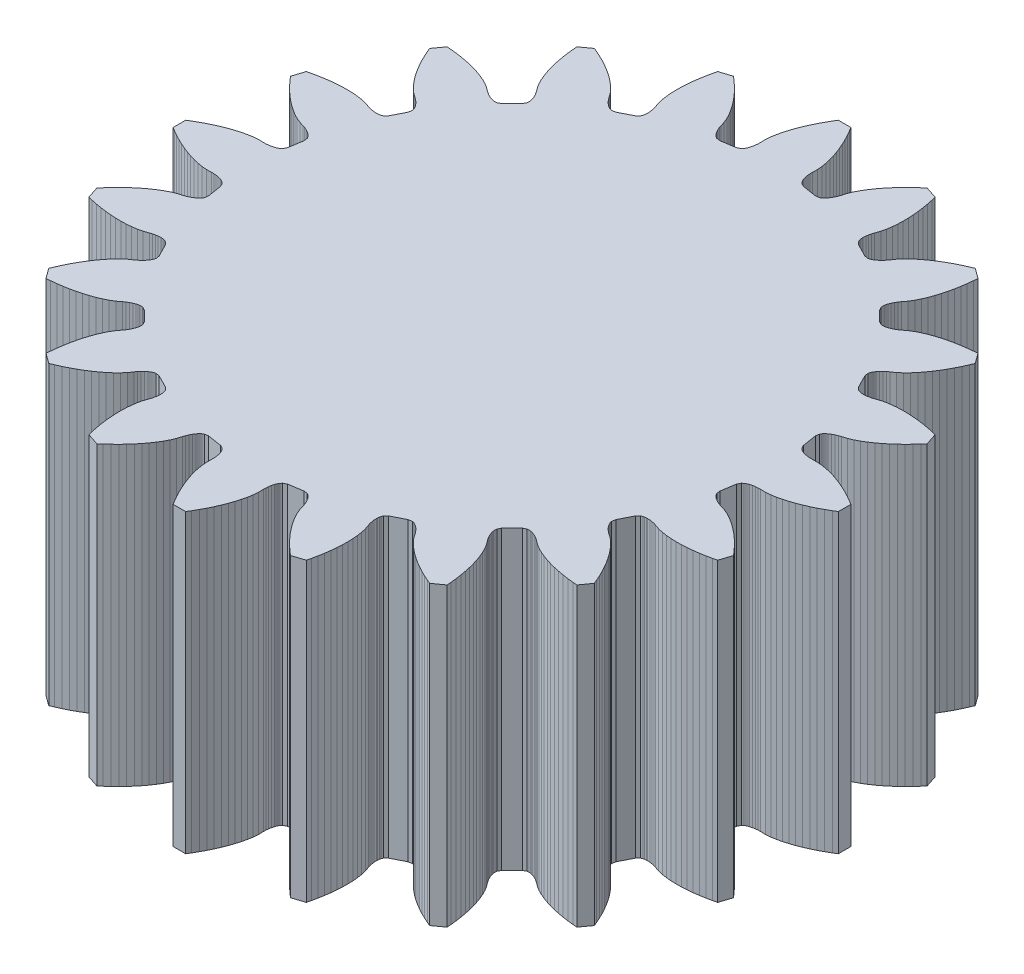
SolidWorks part; units mm, degrees
ref_plane "Front Plane" through (0, 0, 0) normal (0, 0, 1) x (1, 0, 0)
ref_plane "Top Plane" through (0, 0, 0) normal (0, 1, 0) x (1, 0, 0)
ref_plane "Right Plane" through (0, 0, 0) normal (1, 0, 0) x (0, 0, -1)
sketch "Sketch1" plane through (0, 0, 0) normal (0, 1, 0) x (1, 0, 0)
  line L0 (19.9269, 12.3554) -> (19.9815, 12.2461)
  line L1 (19.9815, 12.2461) -> (20.0271, 12.2067)
  line L2 (20.0271, 12.2067) -> (20.0711, 12.1796)
  line L3 (20.0711, 12.1796) -> (20.1144, 12.1591)
  line L4 (20.1144, 12.1591) -> (20.1571, 12.1432)
  line L5 (20.1571, 12.1432) -> (20.2414, 12.1206)
  line L6 (20.2414, 12.1206) -> (20.3248, 12.107)
  line L7 (20.3248, 12.107) -> (20.4075, 12.1)
  line L8 (20.4075, 12.1) -> (20.4897, 12.0984)
  line L9 (20.4897, 12.0984) -> (20.6534, 12.1025)
  line L10 (20.6534, 12.1025) -> (20.8187, 12.0882)
  line L11 (20.8187, 12.0882) -> (20.9851, 12.06)
  line L12 (20.9851, 12.06) -> (21.1522, 12.0208)
  line L13 (21.1522, 12.0208) -> (21.3198, 11.9721)
  line L14 (21.3198, 11.9721) -> (21.4876, 11.9147)
  line L15 (21.4876, 11.9147) -> (21.6554, 11.8491)
  line L16 (21.6554, 11.8491) -> (21.823, 11.7758)
  line L17 (21.823, 11.7758) -> (21.9904, 11.695)
  line L18 (21.9904, 11.695) -> (22.1573, 11.6069)
  line L19 (22.1573, 11.6069) -> (22.3236, 11.5119)
  line L20 (22.3236, 11.5119) -> (22.4478, 11.4361)
  line L21 (22.4478, 11.4361) -> (22.4478, 11.0138)
  line L22 (22.4478, 11.0138) -> (22.3236, 10.9379)
  line L23 (22.3236, 10.9379) -> (22.1573, 10.8429)
  line L24 (22.1573, 10.8429) -> (21.9904, 10.7549)
  line L25 (21.9904, 10.7549) -> (21.823, 10.6741)
  line L26 (21.823, 10.6741) -> (21.6554, 10.6007)
  line L27 (21.6554, 10.6007) -> (21.4876, 10.5351)
  line L28 (21.4876, 10.5351) -> (21.3198, 10.4777)
  line L29 (21.3198, 10.4777) -> (21.1522, 10.429)
  line L30 (21.1522, 10.429) -> (20.9851, 10.3898)
  line L31 (20.9851, 10.3898) -> (20.8187, 10.3616)
  line L32 (20.8187, 10.3616) -> (20.6534, 10.3473)
  line L33 (20.6534, 10.3473) -> (20.4897, 10.3514)
  line L34 (20.4897, 10.3514) -> (20.4075, 10.3498)
  line L35 (20.4075, 10.3498) -> (20.3248, 10.3428)
  line L36 (20.3248, 10.3428) -> (20.2414, 10.3292)
  line L37 (20.2414, 10.3292) -> (20.1571, 10.3066)
  line L38 (20.1571, 10.3066) -> (20.1144, 10.2907)
  line L39 (20.1144, 10.2907) -> (20.0711, 10.2703)
  line L40 (20.0711, 10.2703) -> (20.0271, 10.2431)
  line L41 (20.0271, 10.2431) -> (19.9815, 10.2037)
  line L42 (19.9815, 10.2037) -> (19.9269, 10.0944)
  line L43 (19.9269, 10.0944) -> (19.8503, 9.611)
  line L44 (19.8503, 9.611) -> (19.8685, 9.4902)
  line L45 (19.8685, 9.4902) -> (19.8997, 9.4386)
  line L46 (19.8997, 9.4386) -> (19.9332, 9.3992)
  line L47 (19.9332, 9.3992) -> (19.968, 9.3664)
  line L48 (19.968, 9.3664) -> (20.0037, 9.338)
  line L49 (20.0037, 9.338) -> (20.0769, 9.2905)
  line L50 (20.0769, 9.2905) -> (20.152, 9.2518)
  line L51 (20.152, 9.2518) -> (20.2285, 9.2196)
  line L52 (20.2285, 9.2196) -> (20.3062, 9.1927)
  line L53 (20.3062, 9.1927) -> (20.4631, 9.146)
  line L54 (20.4631, 9.146) -> (20.6159, 9.0813)
  line L55 (20.6159, 9.0813) -> (20.7655, 9.003)
  line L56 (20.7655, 9.003) -> (20.9123, 8.9141)
  line L57 (20.9123, 8.9141) -> (21.0566, 8.8161)
  line L58 (21.0566, 8.8161) -> (21.1984, 8.7096)
  line L59 (21.1984, 8.7096) -> (21.3378, 8.5954)
  line L60 (21.3378, 8.5954) -> (21.4746, 8.4738)
  line L61 (21.4746, 8.4738) -> (21.6088, 8.3452)
  line L62 (21.6088, 8.3452) -> (21.7403, 8.2099)
  line L63 (21.7403, 8.2099) -> (21.8691, 8.0681)
  line L64 (21.8691, 8.0681) -> (21.9638, 7.9577)
  line L65 (21.9638, 7.9577) -> (21.8333, 7.556)
  line L66 (21.8333, 7.556) -> (21.6917, 7.5223)
  line L67 (21.6917, 7.5223) -> (21.5042, 7.4833)
  line L68 (21.5042, 7.4833) -> (21.3183, 7.4511)
  line L69 (21.3183, 7.4511) -> (21.1341, 7.426)
  line L70 (21.1341, 7.426) -> (20.952, 7.4081)
  line L71 (20.952, 7.4081) -> (20.7721, 7.3975)
  line L72 (20.7721, 7.3975) -> (20.5948, 7.3948)
  line L73 (20.5948, 7.3948) -> (20.4204, 7.4002)
  line L74 (20.4204, 7.4002) -> (20.2493, 7.4146)
  line L75 (20.2493, 7.4146) -> (20.0824, 7.4392)
  line L76 (20.0824, 7.4392) -> (19.9207, 7.4767)
  line L77 (19.9207, 7.4767) -> (19.7663, 7.5312)
  line L78 (19.7663, 7.5312) -> (19.6877, 7.555)
  line L79 (19.6877, 7.555) -> (19.6068, 7.5739)
  line L80 (19.6068, 7.5739) -> (19.5233, 7.5868)
  line L81 (19.5233, 7.5868) -> (19.4362, 7.5914)
  line L82 (19.4362, 7.5914) -> (19.3906, 7.5894)
  line L83 (19.3906, 7.5894) -> (19.3432, 7.5834)
  line L84 (19.3432, 7.5834) -> (19.2929, 7.5712)
  line L85 (19.2929, 7.5712) -> (19.2373, 7.5477)
  line L86 (19.2373, 7.5477) -> (19.1516, 7.4607)
  line L87 (19.1516, 7.4607) -> (18.9294, 7.0246)
  line L88 (18.9294, 7.0246) -> (18.9094, 6.9041)
  line L89 (18.9094, 6.9041) -> (18.9231, 6.8454)
  line L90 (18.9231, 6.8454) -> (18.9428, 6.7976)
  line L91 (18.9428, 6.7976) -> (18.9657, 6.7556)
  line L92 (18.9657, 6.7556) -> (18.9909, 6.7176)
  line L93 (18.9909, 6.7176) -> (19.0459, 6.6498)
  line L94 (19.0459, 6.6498) -> (19.1054, 6.5898)
  line L95 (19.1054, 6.5898) -> (19.1682, 6.5355)
  line L96 (19.1682, 6.5355) -> (19.2337, 6.4859)
  line L97 (19.2337, 6.4859) -> (19.3685, 6.393)
  line L98 (19.3685, 6.393) -> (19.4938, 6.2843)
  line L99 (19.4938, 6.2843) -> (19.6119, 6.1636)
  line L100 (19.6119, 6.1636) -> (19.7241, 6.0337)
  line L101 (19.7241, 6.0337) -> (19.831, 5.8958)
  line L102 (19.831, 5.8958) -> (19.933, 5.7507)
  line L103 (19.933, 5.7507) -> (20.0302, 5.599)
  line L104 (20.0302, 5.599) -> (20.1228, 5.4411)
  line L105 (20.1228, 5.4411) -> (20.2107, 5.2774)
  line L106 (20.2107, 5.2774) -> (20.294, 5.1081)
  line L107 (20.294, 5.1081) -> (20.3726, 4.9334)
  line L108 (20.3726, 4.9334) -> (20.4286, 4.7991)
  line L109 (20.4286, 4.7991) -> (20.1803, 4.4574)
  line L110 (20.1803, 4.4574) -> (20.0353, 4.4691)
  line L111 (20.0353, 4.4691) -> (19.8449, 4.4899)
  line L112 (19.8449, 4.4899) -> (19.6581, 4.5168)
  line L113 (19.6581, 4.5168) -> (19.4752, 4.5498)
  line L114 (19.4752, 4.5498) -> (19.2964, 4.589)
  line L115 (19.2964, 4.589) -> (19.1221, 4.6346)
  line L116 (19.1221, 4.6346) -> (18.9526, 4.6868)
  line L117 (18.9526, 4.6868) -> (18.7885, 4.7459)
  line L118 (18.7885, 4.7459) -> (18.6302, 4.8124)
  line L119 (18.6302, 4.8124) -> (18.479, 4.8874)
  line L120 (18.479, 4.8874) -> (18.3369, 4.973)
  line L121 (18.3369, 4.973) -> (18.2069, 5.0725)
  line L122 (18.2069, 5.0725) -> (18.1394, 5.1195)
  line L123 (18.1394, 5.1195) -> (18.0684, 5.1625)
  line L124 (18.0684, 5.1625) -> (17.9929, 5.2005)
  line L125 (17.9929, 5.2005) -> (17.9114, 5.2318)
  line L126 (17.9114, 5.2318) -> (17.8675, 5.244)
  line L127 (17.8675, 5.244) -> (17.8205, 5.2529)
  line L128 (17.8205, 5.2529) -> (17.7689, 5.2568)
  line L129 (17.7689, 5.2568) -> (17.7089, 5.2517)
  line L130 (17.7089, 5.2517) -> (17.6005, 5.1954)
  line L131 (17.6005, 5.1954) -> (17.2544, 4.8494)
  line L132 (17.2544, 4.8494) -> (17.1981, 4.7409)
  line L133 (17.1981, 4.7409) -> (17.193, 4.6809)
  line L134 (17.193, 4.6809) -> (17.1969, 4.6293)
  line L135 (17.1969, 4.6293) -> (17.2058, 4.5823)
  line L136 (17.2058, 4.5823) -> (17.218, 4.5384)
  line L137 (17.218, 4.5384) -> (17.2493, 4.4569)
  line L138 (17.2493, 4.4569) -> (17.2873, 4.3814)
  line L139 (17.2873, 4.3814) -> (17.3303, 4.3104)
  line L140 (17.3303, 4.3104) -> (17.3773, 4.2429)
  line L141 (17.3773, 4.2429) -> (17.4768, 4.113)
  line L142 (17.4768, 4.113) -> (17.5624, 3.9708)
  line L143 (17.5624, 3.9708) -> (17.6374, 3.8196)
  line L144 (17.6374, 3.8196) -> (17.7039, 3.6614)
  line L145 (17.7039, 3.6614) -> (17.763, 3.4972)
  line L146 (17.763, 3.4972) -> (17.8152, 3.3277)
  line L147 (17.8152, 3.3277) -> (17.8608, 3.1534)
  line L148 (17.8608, 3.1534) -> (17.9, 2.9746)
  line L149 (17.9, 2.9746) -> (17.933, 2.7917)
  line L150 (17.933, 2.7917) -> (17.9599, 2.6049)
  line L151 (17.9599, 2.6049) -> (17.9807, 2.4145)
  line L152 (17.9807, 2.4145) -> (17.9924, 2.2695)
  line L153 (17.9924, 2.2695) -> (17.6507, 2.0213)
  line L154 (17.6507, 2.0213) -> (17.5164, 2.0772)
  line L155 (17.5164, 2.0772) -> (17.3418, 2.1559)
  line L156 (17.3418, 2.1559) -> (17.1725, 2.2391)
  line L157 (17.1725, 2.2391) -> (17.0087, 2.327)
  line L158 (17.0087, 2.327) -> (16.8508, 2.4196)
  line L159 (16.8508, 2.4196) -> (16.6991, 2.5168)
  line L160 (16.6991, 2.5168) -> (16.554, 2.6188)
  line L161 (16.554, 2.6188) -> (16.4161, 2.7257)
  line L162 (16.4161, 2.7257) -> (16.2862, 2.8379)
  line L163 (16.2862, 2.8379) -> (16.1656, 2.956)
  line L164 (16.1656, 2.956) -> (16.0568, 3.0813)
  line L165 (16.0568, 3.0813) -> (15.964, 3.2161)
  line L166 (15.964, 3.2161) -> (15.9143, 3.2816)
  line L167 (15.9143, 3.2816) -> (15.8601, 3.3444)
  line L168 (15.8601, 3.3444) -> (15.8, 3.4039)
  line L169 (15.8, 3.4039) -> (15.7322, 3.4589)
  line L170 (15.7322, 3.4589) -> (15.6942, 3.4841)
  line L171 (15.6942, 3.4841) -> (15.6523, 3.507)
  line L172 (15.6523, 3.507) -> (15.6044, 3.5267)
  line L173 (15.6044, 3.5267) -> (15.5457, 3.5404)
  line L174 (15.5457, 3.5404) -> (15.4252, 3.5204)
  line L175 (15.4252, 3.5204) -> (14.9891, 3.2982)
  line L176 (14.9891, 3.2982) -> (14.9021, 3.2125)
  line L177 (14.9021, 3.2125) -> (14.8787, 3.1569)
  line L178 (14.8787, 3.1569) -> (14.8665, 3.1067)
  line L179 (14.8665, 3.1067) -> (14.8604, 3.0592)
  line L180 (14.8604, 3.0592) -> (14.8584, 3.0137)
  line L181 (14.8584, 3.0137) -> (14.863, 2.9265)
  line L182 (14.863, 2.9265) -> (14.8759, 2.843)
  line L183 (14.8759, 2.843) -> (14.8948, 2.7622)
  line L184 (14.8948, 2.7622) -> (14.9186, 2.6835)
  line L185 (14.9186, 2.6835) -> (14.9731, 2.5291)
  line L186 (14.9731, 2.5291) -> (15.0106, 2.3675)
  line L187 (15.0106, 2.3675) -> (15.0352, 2.2005)
  line L188 (15.0352, 2.2005) -> (15.0496, 2.0294)
  line L189 (15.0496, 2.0294) -> (15.055, 1.855)
  line L190 (15.055, 1.855) -> (15.0523, 1.6777)
  line L191 (15.0523, 1.6777) -> (15.0418, 1.4978)
  line L192 (15.0418, 1.4978) -> (15.0238, 1.3157)
  line L193 (15.0238, 1.3157) -> (14.9987, 1.1315)
  line L194 (14.9987, 1.1315) -> (14.9665, 0.9456)
  line L195 (14.9665, 0.9456) -> (14.9275, 0.7581)
  line L196 (14.9275, 0.7581) -> (14.8938, 0.6165)
  line L197 (14.8938, 0.6165) -> (14.4922, 0.486)
  line L198 (14.4922, 0.486) -> (14.3817, 0.5807)
  line L199 (14.3817, 0.5807) -> (14.2399, 0.7095)
  line L200 (14.2399, 0.7095) -> (14.1046, 0.841)
  line L201 (14.1046, 0.841) -> (13.976, 0.9752)
  line L202 (13.976, 0.9752) -> (13.8544, 1.112)
  line L203 (13.8544, 1.112) -> (13.7402, 1.2514)
  line L204 (13.7402, 1.2514) -> (13.6338, 1.3932)
  line L205 (13.6338, 1.3932) -> (13.5357, 1.5375)
  line L206 (13.5357, 1.5375) -> (13.4468, 1.6844)
  line L207 (13.4468, 1.6844) -> (13.3685, 1.8339)
  line L208 (13.3685, 1.8339) -> (13.3038, 1.9867)
  line L209 (13.3038, 1.9867) -> (13.2572, 2.1436)
  line L210 (13.2572, 2.1436) -> (13.2302, 2.2213)
  line L211 (13.2302, 2.2213) -> (13.198, 2.2978)
  line L212 (13.198, 2.2978) -> (13.1593, 2.3729)
  line L213 (13.1593, 2.3729) -> (13.1118, 2.4461)
  line L214 (13.1118, 2.4461) -> (13.0834, 2.4818)
  line L215 (13.0834, 2.4818) -> (13.0506, 2.5166)
  line L216 (13.0506, 2.5166) -> (13.0112, 2.5502)
  line L217 (13.0112, 2.5502) -> (12.9596, 2.5813)
  line L218 (12.9596, 2.5813) -> (12.8388, 2.5995)
  line L219 (12.8388, 2.5995) -> (12.3554, 2.5229)
  line L220 (12.3554, 2.5229) -> (12.2461, 2.4683)
  line L221 (12.2461, 2.4683) -> (12.2067, 2.4227)
  line L222 (12.2067, 2.4227) -> (12.1796, 2.3787)
  line L223 (12.1796, 2.3787) -> (12.1591, 2.3354)
  line L224 (12.1591, 2.3354) -> (12.1432, 2.2927)
  line L225 (12.1432, 2.2927) -> (12.1206, 2.2084)
  line L226 (12.1206, 2.2084) -> (12.107, 2.125)
  line L227 (12.107, 2.125) -> (12.1, 2.0423)
  line L228 (12.1, 2.0423) -> (12.0984, 1.9601)
  line L229 (12.0984, 1.9601) -> (12.1025, 1.7965)
  line L230 (12.1025, 1.7965) -> (12.0882, 1.6311)
  line L231 (12.0882, 1.6311) -> (12.06, 1.4647)
  line L232 (12.06, 1.4647) -> (12.0208, 1.2976)
  line L233 (12.0208, 1.2976) -> (11.9721, 1.13)
  line L234 (11.9721, 1.13) -> (11.9147, 0.9623)
  line L235 (11.9147, 0.9623) -> (11.8491, 0.7944)
  line L236 (11.8491, 0.7944) -> (11.7758, 0.6268)
  line L237 (11.7758, 0.6268) -> (11.695, 0.4594)
  line L238 (11.695, 0.4594) -> (11.6069, 0.2925)
  line L239 (11.6069, 0.2925) -> (11.5119, 0.1262)
  line L240 (11.5119, 0.1262) -> (11.4361, 0.002)
  line L241 (11.4361, 0.002) -> (11.0138, 0.002)
  line L242 (11.0138, 0.002) -> (10.9379, 0.1262)
  line L243 (10.9379, 0.1262) -> (10.8429, 0.2925)
  line L244 (10.8429, 0.2925) -> (10.7549, 0.4594)
  line L245 (10.7549, 0.4594) -> (10.6741, 0.6268)
  line L246 (10.6741, 0.6268) -> (10.6007, 0.7944)
  line L247 (10.6007, 0.7944) -> (10.5351, 0.9623)
  line L248 (10.5351, 0.9623) -> (10.4777, 1.13)
  line L249 (10.4777, 1.13) -> (10.429, 1.2976)
  line L250 (10.429, 1.2976) -> (10.3898, 1.4647)
  line L251 (10.3898, 1.4647) -> (10.3616, 1.6311)
  line L252 (10.3616, 1.6311) -> (10.3473, 1.7965)
  line L253 (10.3473, 1.7965) -> (10.3514, 1.9601)
  line L254 (10.3514, 1.9601) -> (10.3498, 2.0423)
  line L255 (10.3498, 2.0423) -> (10.3428, 2.125)
  line L256 (10.3428, 2.125) -> (10.3292, 2.2084)
  line L257 (10.3292, 2.2084) -> (10.3066, 2.2927)
  line L258 (10.3066, 2.2927) -> (10.2907, 2.3354)
  line L259 (10.2907, 2.3354) -> (10.2703, 2.3787)
  line L260 (10.2703, 2.3787) -> (10.2431, 2.4227)
  line L261 (10.2431, 2.4227) -> (10.2037, 2.4683)
  line L262 (10.2037, 2.4683) -> (10.0944, 2.5229)
  line L263 (10.0944, 2.5229) -> (9.611, 2.5995)
  line L264 (9.611, 2.5995) -> (9.4902, 2.5813)
  line L265 (9.4902, 2.5813) -> (9.4386, 2.5502)
  line L266 (9.4386, 2.5502) -> (9.3992, 2.5166)
  line L267 (9.3992, 2.5166) -> (9.3664, 2.4818)
  line L268 (9.3664, 2.4818) -> (9.338, 2.4461)
  line L269 (9.338, 2.4461) -> (9.2905, 2.3729)
  line L270 (9.2905, 2.3729) -> (9.2518, 2.2978)
  line L271 (9.2518, 2.2978) -> (9.2196, 2.2213)
  line L272 (9.2196, 2.2213) -> (9.1927, 2.1436)
  line L273 (9.1927, 2.1436) -> (9.146, 1.9867)
  line L274 (9.146, 1.9867) -> (9.0813, 1.8339)
  line L275 (9.0813, 1.8339) -> (9.003, 1.6844)
  line L276 (9.003, 1.6844) -> (8.9141, 1.5375)
  line L277 (8.9141, 1.5375) -> (8.8161, 1.3932)
  line L278 (8.8161, 1.3932) -> (8.7096, 1.2514)
  line L279 (8.7096, 1.2514) -> (8.5954, 1.112)
  line L280 (8.5954, 1.112) -> (8.4738, 0.9752)
  line L281 (8.4738, 0.9752) -> (8.3452, 0.841)
  line L282 (8.3452, 0.841) -> (8.2099, 0.7095)
  line L283 (8.2099, 0.7095) -> (8.0681, 0.5807)
  line L284 (8.0681, 0.5807) -> (7.9577, 0.486)
  line L285 (7.9577, 0.486) -> (7.556, 0.6165)
  line L286 (7.556, 0.6165) -> (7.5223, 0.7581)
  line L287 (7.5223, 0.7581) -> (7.4833, 0.9456)
  line L288 (7.4833, 0.9456) -> (7.4511, 1.1315)
  line L289 (7.4511, 1.1315) -> (7.426, 1.3157)
  line L290 (7.426, 1.3157) -> (7.4081, 1.4978)
  line L291 (7.4081, 1.4978) -> (7.3975, 1.6777)
  line L292 (7.3975, 1.6777) -> (7.3948, 1.855)
  line L293 (7.3948, 1.855) -> (7.4002, 2.0294)
  line L294 (7.4002, 2.0294) -> (7.4146, 2.2005)
  line L295 (7.4146, 2.2005) -> (7.4392, 2.3675)
  line L296 (7.4392, 2.3675) -> (7.4767, 2.5291)
  line L297 (7.4767, 2.5291) -> (7.5312, 2.6835)
  line L298 (7.5312, 2.6835) -> (7.555, 2.7622)
  line L299 (7.555, 2.7622) -> (7.5739, 2.843)
  line L300 (7.5739, 2.843) -> (7.5868, 2.9265)
  line L301 (7.5868, 2.9265) -> (7.5914, 3.0137)
  line L302 (7.5914, 3.0137) -> (7.5894, 3.0592)
  line L303 (7.5894, 3.0592) -> (7.5834, 3.1067)
  line L304 (7.5834, 3.1067) -> (7.5712, 3.1569)
  line L305 (7.5712, 3.1569) -> (7.5477, 3.2125)
  line L306 (7.5477, 3.2125) -> (7.4607, 3.2982)
  line L307 (7.4607, 3.2982) -> (7.0246, 3.5204)
  line L308 (7.0246, 3.5204) -> (6.9041, 3.5404)
  line L309 (6.9041, 3.5404) -> (6.8454, 3.5267)
  line L310 (6.8454, 3.5267) -> (6.7976, 3.507)
  line L311 (6.7976, 3.507) -> (6.7556, 3.4841)
  line L312 (6.7556, 3.4841) -> (6.7176, 3.4589)
  line L313 (6.7176, 3.4589) -> (6.6498, 3.4039)
  line L314 (6.6498, 3.4039) -> (6.5898, 3.3444)
  line L315 (6.5898, 3.3444) -> (6.5355, 3.2816)
  line L316 (6.5355, 3.2816) -> (6.4859, 3.2161)
  line L317 (6.4859, 3.2161) -> (6.393, 3.0813)
  line L318 (6.393, 3.0813) -> (6.2843, 2.956)
  line L319 (6.2843, 2.956) -> (6.1636, 2.8379)
  line L320 (6.1636, 2.8379) -> (6.0337, 2.7257)
  line L321 (6.0337, 2.7257) -> (5.8958, 2.6188)
  line L322 (5.8958, 2.6188) -> (5.7507, 2.5168)
  line L323 (5.7507, 2.5168) -> (5.599, 2.4196)
  line L324 (5.599, 2.4196) -> (5.4411, 2.327)
  line L325 (5.4411, 2.327) -> (5.2774, 2.2391)
  line L326 (5.2774, 2.2391) -> (5.1081, 2.1559)
  line L327 (5.1081, 2.1559) -> (4.9334, 2.0772)
  line L328 (4.9334, 2.0772) -> (4.7991, 2.0213)
  line L329 (4.7991, 2.0213) -> (4.4574, 2.2695)
  line L330 (4.4574, 2.2695) -> (4.4691, 2.4145)
  line L331 (4.4691, 2.4145) -> (4.4899, 2.6049)
  line L332 (4.4899, 2.6049) -> (4.5168, 2.7917)
  line L333 (4.5168, 2.7917) -> (4.5498, 2.9746)
  line L334 (4.5498, 2.9746) -> (4.589, 3.1534)
  line L335 (4.589, 3.1534) -> (4.6346, 3.3277)
  line L336 (4.6346, 3.3277) -> (4.6868, 3.4972)
  line L337 (4.6868, 3.4972) -> (4.7459, 3.6614)
  line L338 (4.7459, 3.6614) -> (4.8124, 3.8196)
  line L339 (4.8124, 3.8196) -> (4.8874, 3.9708)
  line L340 (4.8874, 3.9708) -> (4.973, 4.113)
  line L341 (4.973, 4.113) -> (5.0725, 4.2429)
  line L342 (5.0725, 4.2429) -> (5.1195, 4.3104)
  line L343 (5.1195, 4.3104) -> (5.1625, 4.3814)
  line L344 (5.1625, 4.3814) -> (5.2005, 4.4569)
  line L345 (5.2005, 4.4569) -> (5.2318, 4.5384)
  line L346 (5.2318, 4.5384) -> (5.244, 4.5823)
  line L347 (5.244, 4.5823) -> (5.2529, 4.6293)
  line L348 (5.2529, 4.6293) -> (5.2568, 4.6809)
  line L349 (5.2568, 4.6809) -> (5.2517, 4.7409)
  line L350 (5.2517, 4.7409) -> (5.1954, 4.8494)
  line L351 (5.1954, 4.8494) -> (4.8494, 5.1954)
  line L352 (4.8494, 5.1954) -> (4.7409, 5.2517)
  line L353 (4.7409, 5.2517) -> (4.6809, 5.2568)
  line L354 (4.6809, 5.2568) -> (4.6293, 5.2529)
  line L355 (4.6293, 5.2529) -> (4.5823, 5.244)
  line L356 (4.5823, 5.244) -> (4.5384, 5.2318)
  line L357 (4.5384, 5.2318) -> (4.4569, 5.2005)
  line L358 (4.4569, 5.2005) -> (4.3814, 5.1625)
  line L359 (4.3814, 5.1625) -> (4.3104, 5.1195)
  line L360 (4.3104, 5.1195) -> (4.2429, 5.0725)
  line L361 (4.2429, 5.0725) -> (4.113, 4.973)
  line L362 (4.113, 4.973) -> (3.9708, 4.8874)
  line L363 (3.9708, 4.8874) -> (3.8196, 4.8124)
  line L364 (3.8196, 4.8124) -> (3.6614, 4.7459)
  line L365 (3.6614, 4.7459) -> (3.4972, 4.6868)
  line L366 (3.4972, 4.6868) -> (3.3277, 4.6346)
  line L367 (3.3277, 4.6346) -> (3.1534, 4.589)
  line L368 (3.1534, 4.589) -> (2.9746, 4.5498)
  line L369 (2.9746, 4.5498) -> (2.7917, 4.5168)
  line L370 (2.7917, 4.5168) -> (2.6049, 4.4899)
  line L371 (2.6049, 4.4899) -> (2.4145, 4.4691)
  line L372 (2.4145, 4.4691) -> (2.2695, 4.4574)
  line L373 (2.2695, 4.4574) -> (2.0213, 4.7991)
  line L374 (2.0213, 4.7991) -> (2.0772, 4.9334)
  line L375 (2.0772, 4.9334) -> (2.1559, 5.1081)
  line L376 (2.1559, 5.1081) -> (2.2391, 5.2774)
  line L377 (2.2391, 5.2774) -> (2.327, 5.4411)
  line L378 (2.327, 5.4411) -> (2.4196, 5.599)
  line L379 (2.4196, 5.599) -> (2.5168, 5.7507)
  line L380 (2.5168, 5.7507) -> (2.6188, 5.8958)
  line L381 (2.6188, 5.8958) -> (2.7257, 6.0337)
  line L382 (2.7257, 6.0337) -> (2.8379, 6.1636)
  line L383 (2.8379, 6.1636) -> (2.956, 6.2843)
  line L384 (2.956, 6.2843) -> (3.0813, 6.393)
  line L385 (3.0813, 6.393) -> (3.2161, 6.4859)
  line L386 (3.2161, 6.4859) -> (3.2816, 6.5355)
  line L387 (3.2816, 6.5355) -> (3.3444, 6.5898)
  line L388 (3.3444, 6.5898) -> (3.4039, 6.6498)
  line L389 (3.4039, 6.6498) -> (3.4589, 6.7176)
  line L390 (3.4589, 6.7176) -> (3.4841, 6.7556)
  line L391 (3.4841, 6.7556) -> (3.507, 6.7976)
  line L392 (3.507, 6.7976) -> (3.5267, 6.8454)
  line L393 (3.5267, 6.8454) -> (3.5404, 6.9041)
  line L394 (3.5404, 6.9041) -> (3.5204, 7.0246)
  line L395 (3.5204, 7.0246) -> (3.2982, 7.4607)
  line L396 (3.2982, 7.4607) -> (3.2125, 7.5477)
  line L397 (3.2125, 7.5477) -> (3.1569, 7.5712)
  line L398 (3.1569, 7.5712) -> (3.1067, 7.5834)
  line L399 (3.1067, 7.5834) -> (3.0592, 7.5894)
  line L400 (3.0592, 7.5894) -> (3.0137, 7.5914)
  line L401 (3.0137, 7.5914) -> (2.9265, 7.5868)
  line L402 (2.9265, 7.5868) -> (2.843, 7.5739)
  line L403 (2.843, 7.5739) -> (2.7622, 7.555)
  line L404 (2.7622, 7.555) -> (2.6835, 7.5312)
  line L405 (2.6835, 7.5312) -> (2.5291, 7.4767)
  line L406 (2.5291, 7.4767) -> (2.3675, 7.4392)
  line L407 (2.3675, 7.4392) -> (2.2005, 7.4146)
  line L408 (2.2005, 7.4146) -> (2.0294, 7.4002)
  line L409 (2.0294, 7.4002) -> (1.855, 7.3948)
  line L410 (1.855, 7.3948) -> (1.6777, 7.3975)
  line L411 (1.6777, 7.3975) -> (1.4978, 7.4081)
  line L412 (1.4978, 7.4081) -> (1.3157, 7.426)
  line L413 (1.3157, 7.426) -> (1.1315, 7.4511)
  line L414 (1.1315, 7.4511) -> (0.9456, 7.4833)
  line L415 (0.9456, 7.4833) -> (0.7581, 7.5223)
  line L416 (0.7581, 7.5223) -> (0.6165, 7.556)
  line L417 (0.6165, 7.556) -> (0.486, 7.9577)
  line L418 (0.486, 7.9577) -> (0.5807, 8.0681)
  line L419 (0.5807, 8.0681) -> (0.7095, 8.2099)
  line L420 (0.7095, 8.2099) -> (0.841, 8.3452)
  line L421 (0.841, 8.3452) -> (0.9752, 8.4738)
  line L422 (0.9752, 8.4738) -> (1.112, 8.5954)
  line L423 (1.112, 8.5954) -> (1.2514, 8.7096)
  line L424 (1.2514, 8.7096) -> (1.3932, 8.8161)
  line L425 (1.3932, 8.8161) -> (1.5375, 8.9141)
  line L426 (1.5375, 8.9141) -> (1.6844, 9.003)
  line L427 (1.6844, 9.003) -> (1.8339, 9.0813)
  line L428 (1.8339, 9.0813) -> (1.9867, 9.146)
  line L429 (1.9867, 9.146) -> (2.1436, 9.1927)
  line L430 (2.1436, 9.1927) -> (2.2213, 9.2196)
  line L431 (2.2213, 9.2196) -> (2.2978, 9.2518)
  line L432 (2.2978, 9.2518) -> (2.3729, 9.2905)
  line L433 (2.3729, 9.2905) -> (2.4461, 9.338)
  line L434 (2.4461, 9.338) -> (2.4818, 9.3664)
  line L435 (2.4818, 9.3664) -> (2.5166, 9.3992)
  line L436 (2.5166, 9.3992) -> (2.5502, 9.4386)
  line L437 (2.5502, 9.4386) -> (2.5813, 9.4902)
  line L438 (2.5813, 9.4902) -> (2.5995, 9.611)
  line L439 (2.5995, 9.611) -> (2.5229, 10.0944)
  line L440 (2.5229, 10.0944) -> (2.4683, 10.2037)
  line L441 (2.4683, 10.2037) -> (2.4227, 10.2431)
  line L442 (2.4227, 10.2431) -> (2.3787, 10.2703)
  line L443 (2.3787, 10.2703) -> (2.3354, 10.2907)
  line L444 (2.3354, 10.2907) -> (2.2927, 10.3066)
  line L445 (2.2927, 10.3066) -> (2.2084, 10.3292)
  line L446 (2.2084, 10.3292) -> (2.125, 10.3428)
  line L447 (2.125, 10.3428) -> (2.0423, 10.3498)
  line L448 (2.0423, 10.3498) -> (1.9601, 10.3514)
  line L449 (1.9601, 10.3514) -> (1.7965, 10.3473)
  line L450 (1.7965, 10.3473) -> (1.6311, 10.3616)
  line L451 (1.6311, 10.3616) -> (1.4647, 10.3898)
  line L452 (1.4647, 10.3898) -> (1.2976, 10.429)
  line L453 (1.2976, 10.429) -> (1.13, 10.4777)
  line L454 (1.13, 10.4777) -> (0.9623, 10.5351)
  line L455 (0.9623, 10.5351) -> (0.7944, 10.6007)
  line L456 (0.7944, 10.6007) -> (0.6268, 10.6741)
  line L457 (0.6268, 10.6741) -> (0.4594, 10.7549)
  line L458 (0.4594, 10.7549) -> (0.2925, 10.8429)
  line L459 (0.2925, 10.8429) -> (0.1262, 10.9379)
  line L460 (0.1262, 10.9379) -> (0.002, 11.0138)
  line L461 (0.002, 11.0138) -> (0.002, 11.4361)
  line L462 (0.002, 11.4361) -> (0.1262, 11.5119)
  line L463 (0.1262, 11.5119) -> (0.2925, 11.6069)
  line L464 (0.2925, 11.6069) -> (0.4594, 11.695)
  line L465 (0.4594, 11.695) -> (0.6268, 11.7758)
  line L466 (0.6268, 11.7758) -> (0.7944, 11.8491)
  line L467 (0.7944, 11.8491) -> (0.9623, 11.9147)
  line L468 (0.9623, 11.9147) -> (1.13, 11.9721)
  line L469 (1.13, 11.9721) -> (1.2976, 12.0208)
  line L470 (1.2976, 12.0208) -> (1.4647, 12.06)
  line L471 (1.4647, 12.06) -> (1.6311, 12.0882)
  line L472 (1.6311, 12.0882) -> (1.7965, 12.1025)
  line L473 (1.7965, 12.1025) -> (1.9601, 12.0984)
  line L474 (1.9601, 12.0984) -> (2.0423, 12.1)
  line L475 (2.0423, 12.1) -> (2.125, 12.107)
  line L476 (2.125, 12.107) -> (2.2084, 12.1206)
  line L477 (2.2084, 12.1206) -> (2.2927, 12.1432)
  line L478 (2.2927, 12.1432) -> (2.3354, 12.1591)
  line L479 (2.3354, 12.1591) -> (2.3787, 12.1796)
  line L480 (2.3787, 12.1796) -> (2.4227, 12.2067)
  line L481 (2.4227, 12.2067) -> (2.4683, 12.2461)
  line L482 (2.4683, 12.2461) -> (2.5229, 12.3554)
  line L483 (2.5229, 12.3554) -> (2.5995, 12.8388)
  line L484 (2.5995, 12.8388) -> (2.5813, 12.9596)
  line L485 (2.5813, 12.9596) -> (2.5502, 13.0112)
  line L486 (2.5502, 13.0112) -> (2.5166, 13.0506)
  line L487 (2.5166, 13.0506) -> (2.4818, 13.0834)
  line L488 (2.4818, 13.0834) -> (2.4461, 13.1118)
  line L489 (2.4461, 13.1118) -> (2.3729, 13.1593)
  line L490 (2.3729, 13.1593) -> (2.2978, 13.198)
  line L491 (2.2978, 13.198) -> (2.2213, 13.2302)
  line L492 (2.2213, 13.2302) -> (2.1436, 13.2572)
  line L493 (2.1436, 13.2572) -> (1.9867, 13.3038)
  line L494 (1.9867, 13.3038) -> (1.8339, 13.3685)
  line L495 (1.8339, 13.3685) -> (1.6844, 13.4468)
  line L496 (1.6844, 13.4468) -> (1.5375, 13.5357)
  line L497 (1.5375, 13.5357) -> (1.3932, 13.6338)
  line L498 (1.3932, 13.6338) -> (1.2514, 13.7402)
  line L499 (1.2514, 13.7402) -> (1.112, 13.8544)
  line L500 (1.112, 13.8544) -> (0.9752, 13.976)
  line L501 (0.9752, 13.976) -> (0.841, 14.1046)
  line L502 (0.841, 14.1046) -> (0.7095, 14.2399)
  line L503 (0.7095, 14.2399) -> (0.5807, 14.3817)
  line L504 (0.5807, 14.3817) -> (0.486, 14.4922)
  line L505 (0.486, 14.4922) -> (0.6165, 14.8938)
  line L506 (0.6165, 14.8938) -> (0.7581, 14.9275)
  line L507 (0.7581, 14.9275) -> (0.9456, 14.9665)
  line L508 (0.9456, 14.9665) -> (1.1315, 14.9987)
  line L509 (1.1315, 14.9987) -> (1.3157, 15.0238)
  line L510 (1.3157, 15.0238) -> (1.4978, 15.0418)
  line L511 (1.4978, 15.0418) -> (1.6777, 15.0523)
  line L512 (1.6777, 15.0523) -> (1.855, 15.055)
  line L513 (1.855, 15.055) -> (2.0294, 15.0496)
  line L514 (2.0294, 15.0496) -> (2.2005, 15.0352)
  line L515 (2.2005, 15.0352) -> (2.3675, 15.0106)
  line L516 (2.3675, 15.0106) -> (2.5291, 14.9731)
  line L517 (2.5291, 14.9731) -> (2.6835, 14.9186)
  line L518 (2.6835, 14.9186) -> (2.7622, 14.8948)
  line L519 (2.7622, 14.8948) -> (2.843, 14.8759)
  line L520 (2.843, 14.8759) -> (2.9265, 14.863)
  line L521 (2.9265, 14.863) -> (3.0137, 14.8584)
  line L522 (3.0137, 14.8584) -> (3.0592, 14.8604)
  line L523 (3.0592, 14.8604) -> (3.1067, 14.8665)
  line L524 (3.1067, 14.8665) -> (3.1569, 14.8787)
  line L525 (3.1569, 14.8787) -> (3.2125, 14.9021)
  line L526 (3.2125, 14.9021) -> (3.2982, 14.9891)
  line L527 (3.2982, 14.9891) -> (3.5204, 15.4252)
  line L528 (3.5204, 15.4252) -> (3.5404, 15.5457)
  line L529 (3.5404, 15.5457) -> (3.5267, 15.6044)
  line L530 (3.5267, 15.6044) -> (3.507, 15.6523)
  line L531 (3.507, 15.6523) -> (3.4841, 15.6942)
  line L532 (3.4841, 15.6942) -> (3.4589, 15.7322)
  line L533 (3.4589, 15.7322) -> (3.4039, 15.8)
  line L534 (3.4039, 15.8) -> (3.3444, 15.8601)
  line L535 (3.3444, 15.8601) -> (3.2816, 15.9143)
  line L536 (3.2816, 15.9143) -> (3.2161, 15.964)
  line L537 (3.2161, 15.964) -> (3.0813, 16.0568)
  line L538 (3.0813, 16.0568) -> (2.956, 16.1656)
  line L539 (2.956, 16.1656) -> (2.8379, 16.2862)
  line L540 (2.8379, 16.2862) -> (2.7257, 16.4161)
  line L541 (2.7257, 16.4161) -> (2.6188, 16.554)
  line L542 (2.6188, 16.554) -> (2.5168, 16.6991)
  line L543 (2.5168, 16.6991) -> (2.4196, 16.8508)
  line L544 (2.4196, 16.8508) -> (2.327, 17.0087)
  line L545 (2.327, 17.0087) -> (2.2391, 17.1725)
  line L546 (2.2391, 17.1725) -> (2.1559, 17.3418)
  line L547 (2.1559, 17.3418) -> (2.0772, 17.5164)
  line L548 (2.0772, 17.5164) -> (2.0213, 17.6507)
  line L549 (2.0213, 17.6507) -> (2.2695, 17.9924)
  line L550 (2.2695, 17.9924) -> (2.4145, 17.9807)
  line L551 (2.4145, 17.9807) -> (2.6049, 17.9599)
  line L552 (2.6049, 17.9599) -> (2.7917, 17.933)
  line L553 (2.7917, 17.933) -> (2.9746, 17.9)
  line L554 (2.9746, 17.9) -> (3.1534, 17.8608)
  line L555 (3.1534, 17.8608) -> (3.3277, 17.8152)
  line L556 (3.3277, 17.8152) -> (3.4972, 17.763)
  line L557 (3.4972, 17.763) -> (3.6614, 17.7039)
  line L558 (3.6614, 17.7039) -> (3.8196, 17.6374)
  line L559 (3.8196, 17.6374) -> (3.9708, 17.5624)
  line L560 (3.9708, 17.5624) -> (4.113, 17.4768)
  line L561 (4.113, 17.4768) -> (4.2429, 17.3773)
  line L562 (4.2429, 17.3773) -> (4.3104, 17.3303)
  line L563 (4.3104, 17.3303) -> (4.3814, 17.2873)
  line L564 (4.3814, 17.2873) -> (4.4569, 17.2493)
  line L565 (4.4569, 17.2493) -> (4.5384, 17.218)
  line L566 (4.5384, 17.218) -> (4.5823, 17.2058)
  line L567 (4.5823, 17.2058) -> (4.6293, 17.1969)
  line L568 (4.6293, 17.1969) -> (4.6809, 17.193)
  line L569 (4.6809, 17.193) -> (4.7409, 17.1981)
  line L570 (4.7409, 17.1981) -> (4.8494, 17.2544)
  line L571 (4.8494, 17.2544) -> (5.1954, 17.6005)
  line L572 (5.1954, 17.6005) -> (5.2517, 17.7089)
  line L573 (5.2517, 17.7089) -> (5.2568, 17.7689)
  line L574 (5.2568, 17.7689) -> (5.2529, 17.8205)
  line L575 (5.2529, 17.8205) -> (5.244, 17.8675)
  line L576 (5.244, 17.8675) -> (5.2318, 17.9114)
  line L577 (5.2318, 17.9114) -> (5.2005, 17.9929)
  line L578 (5.2005, 17.9929) -> (5.1625, 18.0684)
  line L579 (5.1625, 18.0684) -> (5.1195, 18.1394)
  line L580 (5.1195, 18.1394) -> (5.0725, 18.2069)
  line L581 (5.0725, 18.2069) -> (4.973, 18.3369)
  line L582 (4.973, 18.3369) -> (4.8874, 18.479)
  line L583 (4.8874, 18.479) -> (4.8124, 18.6302)
  line L584 (4.8124, 18.6302) -> (4.7459, 18.7885)
  line L585 (4.7459, 18.7885) -> (4.6868, 18.9526)
  line L586 (4.6868, 18.9526) -> (4.6346, 19.1221)
  line L587 (4.6346, 19.1221) -> (4.589, 19.2964)
  line L588 (4.589, 19.2964) -> (4.5498, 19.4752)
  line L589 (4.5498, 19.4752) -> (4.5168, 19.6581)
  line L590 (4.5168, 19.6581) -> (4.4899, 19.8449)
  line L591 (4.4899, 19.8449) -> (4.4691, 20.0353)
  line L592 (4.4691, 20.0353) -> (4.4574, 20.1803)
  line L593 (4.4574, 20.1803) -> (4.7991, 20.4286)
  line L594 (4.7991, 20.4286) -> (4.9334, 20.3726)
  line L595 (4.9334, 20.3726) -> (5.1081, 20.294)
  line L596 (5.1081, 20.294) -> (5.2774, 20.2107)
  line L597 (5.2774, 20.2107) -> (5.4411, 20.1228)
  line L598 (5.4411, 20.1228) -> (5.599, 20.0302)
  line L599 (5.599, 20.0302) -> (5.7507, 19.933)
  line L600 (5.7507, 19.933) -> (5.8958, 19.831)
  line L601 (5.8958, 19.831) -> (6.0337, 19.7241)
  line L602 (6.0337, 19.7241) -> (6.1636, 19.6119)
  line L603 (6.1636, 19.6119) -> (6.2843, 19.4938)
  line L604 (6.2843, 19.4938) -> (6.393, 19.3685)
  line L605 (6.393, 19.3685) -> (6.4859, 19.2337)
  line L606 (6.4859, 19.2337) -> (6.5355, 19.1682)
  line L607 (6.5355, 19.1682) -> (6.5898, 19.1054)
  line L608 (6.5898, 19.1054) -> (6.6498, 19.0459)
  line L609 (6.6498, 19.0459) -> (6.7176, 18.9909)
  line L610 (6.7176, 18.9909) -> (6.7556, 18.9657)
  line L611 (6.7556, 18.9657) -> (6.7976, 18.9428)
  line L612 (6.7976, 18.9428) -> (6.8454, 18.9231)
  line L613 (6.8454, 18.9231) -> (6.9041, 18.9094)
  line L614 (6.9041, 18.9094) -> (7.0246, 18.9294)
  line L615 (7.0246, 18.9294) -> (7.4607, 19.1516)
  line L616 (7.4607, 19.1516) -> (7.5477, 19.2373)
  line L617 (7.5477, 19.2373) -> (7.5712, 19.2929)
  line L618 (7.5712, 19.2929) -> (7.5834, 19.3432)
  line L619 (7.5834, 19.3432) -> (7.5894, 19.3906)
  line L620 (7.5894, 19.3906) -> (7.5914, 19.4362)
  line L621 (7.5914, 19.4362) -> (7.5868, 19.5233)
  line L622 (7.5868, 19.5233) -> (7.5739, 19.6068)
  line L623 (7.5739, 19.6068) -> (7.555, 19.6877)
  line L624 (7.555, 19.6877) -> (7.5312, 19.7663)
  line L625 (7.5312, 19.7663) -> (7.4767, 19.9207)
  line L626 (7.4767, 19.9207) -> (7.4392, 20.0824)
  line L627 (7.4392, 20.0824) -> (7.4146, 20.2493)
  line L628 (7.4146, 20.2493) -> (7.4002, 20.4204)
  line L629 (7.4002, 20.4204) -> (7.3948, 20.5948)
  line L630 (7.3948, 20.5948) -> (7.3975, 20.7721)
  line L631 (7.3975, 20.7721) -> (7.4081, 20.952)
  line L632 (7.4081, 20.952) -> (7.426, 21.1341)
  line L633 (7.426, 21.1341) -> (7.4511, 21.3183)
  line L634 (7.4511, 21.3183) -> (7.4833, 21.5042)
  line L635 (7.4833, 21.5042) -> (7.5223, 21.6917)
  line L636 (7.5223, 21.6917) -> (7.556, 21.8333)
  line L637 (7.556, 21.8333) -> (7.9577, 21.9638)
  line L638 (7.9577, 21.9638) -> (8.0681, 21.8691)
  line L639 (8.0681, 21.8691) -> (8.2099, 21.7403)
  line L640 (8.2099, 21.7403) -> (8.3452, 21.6088)
  line L641 (8.3452, 21.6088) -> (8.4738, 21.4746)
  line L642 (8.4738, 21.4746) -> (8.5954, 21.3378)
  line L643 (8.5954, 21.3378) -> (8.7096, 21.1984)
  line L644 (8.7096, 21.1984) -> (8.8161, 21.0566)
  line L645 (8.8161, 21.0566) -> (8.9141, 20.9123)
  line L646 (8.9141, 20.9123) -> (9.003, 20.7655)
  line L647 (9.003, 20.7655) -> (9.0813, 20.6159)
  line L648 (9.0813, 20.6159) -> (9.146, 20.4631)
  line L649 (9.146, 20.4631) -> (9.1927, 20.3062)
  line L650 (9.1927, 20.3062) -> (9.2196, 20.2285)
  line L651 (9.2196, 20.2285) -> (9.2518, 20.152)
  line L652 (9.2518, 20.152) -> (9.2905, 20.0769)
  line L653 (9.2905, 20.0769) -> (9.338, 20.0037)
  line L654 (9.338, 20.0037) -> (9.3664, 19.968)
  line L655 (9.3664, 19.968) -> (9.3992, 19.9332)
  line L656 (9.3992, 19.9332) -> (9.4386, 19.8997)
  line L657 (9.4386, 19.8997) -> (9.4902, 19.8685)
  line L658 (9.4902, 19.8685) -> (9.611, 19.8503)
  line L659 (9.611, 19.8503) -> (10.0944, 19.9269)
  line L660 (10.0944, 19.9269) -> (10.2037, 19.9815)
  line L661 (10.2037, 19.9815) -> (10.2431, 20.0271)
  line L662 (10.2431, 20.0271) -> (10.2703, 20.0711)
  line L663 (10.2703, 20.0711) -> (10.2907, 20.1144)
  line L664 (10.2907, 20.1144) -> (10.3066, 20.1571)
  line L665 (10.3066, 20.1571) -> (10.3292, 20.2414)
  line L666 (10.3292, 20.2414) -> (10.3428, 20.3248)
  line L667 (10.3428, 20.3248) -> (10.3498, 20.4075)
  line L668 (10.3498, 20.4075) -> (10.3514, 20.4897)
  line L669 (10.3514, 20.4897) -> (10.3473, 20.6534)
  line L670 (10.3473, 20.6534) -> (10.3616, 20.8187)
  line L671 (10.3616, 20.8187) -> (10.3898, 20.9851)
  line L672 (10.3898, 20.9851) -> (10.429, 21.1522)
  line L673 (10.429, 21.1522) -> (10.4777, 21.3198)
  line L674 (10.4777, 21.3198) -> (10.5351, 21.4876)
  line L675 (10.5351, 21.4876) -> (10.6007, 21.6554)
  line L676 (10.6007, 21.6554) -> (10.6741, 21.823)
  line L677 (10.6741, 21.823) -> (10.7549, 21.9904)
  line L678 (10.7549, 21.9904) -> (10.8429, 22.1573)
  line L679 (10.8429, 22.1573) -> (10.9379, 22.3236)
  line L680 (10.9379, 22.3236) -> (11.0138, 22.4478)
  line L681 (11.0138, 22.4478) -> (11.4361, 22.4478)
  line L682 (11.4361, 22.4478) -> (11.5119, 22.3236)
  line L683 (11.5119, 22.3236) -> (11.6069, 22.1573)
  line L684 (11.6069, 22.1573) -> (11.695, 21.9904)
  line L685 (11.695, 21.9904) -> (11.7758, 21.823)
  line L686 (11.7758, 21.823) -> (11.8491, 21.6554)
  line L687 (11.8491, 21.6554) -> (11.9147, 21.4876)
  line L688 (11.9147, 21.4876) -> (11.9721, 21.3198)
  line L689 (11.9721, 21.3198) -> (12.0208, 21.1522)
  line L690 (12.0208, 21.1522) -> (12.06, 20.9851)
  line L691 (12.06, 20.9851) -> (12.0882, 20.8187)
  line L692 (12.0882, 20.8187) -> (12.1025, 20.6534)
  line L693 (12.1025, 20.6534) -> (12.0984, 20.4897)
  line L694 (12.0984, 20.4897) -> (12.1, 20.4075)
  line L695 (12.1, 20.4075) -> (12.107, 20.3248)
  line L696 (12.107, 20.3248) -> (12.1206, 20.2414)
  line L697 (12.1206, 20.2414) -> (12.1432, 20.1571)
  line L698 (12.1432, 20.1571) -> (12.1591, 20.1144)
  line L699 (12.1591, 20.1144) -> (12.1796, 20.0711)
  line L700 (12.1796, 20.0711) -> (12.2067, 20.0271)
  line L701 (12.2067, 20.0271) -> (12.2461, 19.9815)
  line L702 (12.2461, 19.9815) -> (12.3554, 19.9269)
  line L703 (12.3554, 19.9269) -> (12.8388, 19.8503)
  line L704 (12.8388, 19.8503) -> (12.9596, 19.8685)
  line L705 (12.9596, 19.8685) -> (13.0112, 19.8997)
  line L706 (13.0112, 19.8997) -> (13.0506, 19.9332)
  line L707 (13.0506, 19.9332) -> (13.0834, 19.968)
  line L708 (13.0834, 19.968) -> (13.1118, 20.0037)
  line L709 (13.1118, 20.0037) -> (13.1593, 20.0769)
  line L710 (13.1593, 20.0769) -> (13.198, 20.152)
  line L711 (13.198, 20.152) -> (13.2302, 20.2285)
  line L712 (13.2302, 20.2285) -> (13.2572, 20.3062)
  line L713 (13.2572, 20.3062) -> (13.3038, 20.4631)
  line L714 (13.3038, 20.4631) -> (13.3685, 20.6159)
  line L715 (13.3685, 20.6159) -> (13.4468, 20.7655)
  line L716 (13.4468, 20.7655) -> (13.5357, 20.9123)
  line L717 (13.5357, 20.9123) -> (13.6338, 21.0566)
  line L718 (13.6338, 21.0566) -> (13.7402, 21.1984)
  line L719 (13.7402, 21.1984) -> (13.8544, 21.3378)
  line L720 (13.8544, 21.3378) -> (13.976, 21.4746)
  line L721 (13.976, 21.4746) -> (14.1046, 21.6088)
  line L722 (14.1046, 21.6088) -> (14.2399, 21.7403)
  line L723 (14.2399, 21.7403) -> (14.3817, 21.8691)
  line L724 (14.3817, 21.8691) -> (14.4922, 21.9638)
  line L725 (14.4922, 21.9638) -> (14.8938, 21.8333)
  line L726 (14.8938, 21.8333) -> (14.9275, 21.6917)
  line L727 (14.9275, 21.6917) -> (14.9665, 21.5042)
  line L728 (14.9665, 21.5042) -> (14.9987, 21.3183)
  line L729 (14.9987, 21.3183) -> (15.0238, 21.1341)
  line L730 (15.0238, 21.1341) -> (15.0418, 20.952)
  line L731 (15.0418, 20.952) -> (15.0523, 20.7721)
  line L732 (15.0523, 20.7721) -> (15.055, 20.5948)
  line L733 (15.055, 20.5948) -> (15.0496, 20.4204)
  line L734 (15.0496, 20.4204) -> (15.0352, 20.2493)
  line L735 (15.0352, 20.2493) -> (15.0106, 20.0824)
  line L736 (15.0106, 20.0824) -> (14.9731, 19.9207)
  line L737 (14.9731, 19.9207) -> (14.9186, 19.7663)
  line L738 (14.9186, 19.7663) -> (14.8948, 19.6877)
  line L739 (14.8948, 19.6877) -> (14.8759, 19.6068)
  line L740 (14.8759, 19.6068) -> (14.863, 19.5233)
  line L741 (14.863, 19.5233) -> (14.8584, 19.4362)
  line L742 (14.8584, 19.4362) -> (14.8604, 19.3906)
  line L743 (14.8604, 19.3906) -> (14.8665, 19.3432)
  line L744 (14.8665, 19.3432) -> (14.8787, 19.2929)
  line L745 (14.8787, 19.2929) -> (14.9021, 19.2373)
  line L746 (14.9021, 19.2373) -> (14.9891, 19.1516)
  line L747 (14.9891, 19.1516) -> (15.4252, 18.9294)
  line L748 (15.4252, 18.9294) -> (15.5457, 18.9094)
  line L749 (15.5457, 18.9094) -> (15.6044, 18.9231)
  line L750 (15.6044, 18.9231) -> (15.6523, 18.9428)
  line L751 (15.6523, 18.9428) -> (15.6942, 18.9657)
  line L752 (15.6942, 18.9657) -> (15.7322, 18.9909)
  line L753 (15.7322, 18.9909) -> (15.8, 19.0459)
  line L754 (15.8, 19.0459) -> (15.8601, 19.1054)
  line L755 (15.8601, 19.1054) -> (15.9143, 19.1682)
  line L756 (15.9143, 19.1682) -> (15.964, 19.2337)
  line L757 (15.964, 19.2337) -> (16.0568, 19.3685)
  line L758 (16.0568, 19.3685) -> (16.1656, 19.4938)
  line L759 (16.1656, 19.4938) -> (16.2862, 19.6119)
  line L760 (16.2862, 19.6119) -> (16.4161, 19.7241)
  line L761 (16.4161, 19.7241) -> (16.554, 19.831)
  line L762 (16.554, 19.831) -> (16.6991, 19.933)
  line L763 (16.6991, 19.933) -> (16.8508, 20.0302)
  line L764 (16.8508, 20.0302) -> (17.0087, 20.1228)
  line L765 (17.0087, 20.1228) -> (17.1725, 20.2107)
  line L766 (17.1725, 20.2107) -> (17.3418, 20.294)
  line L767 (17.3418, 20.294) -> (17.5164, 20.3726)
  line L768 (17.5164, 20.3726) -> (17.6507, 20.4286)
  line L769 (17.6507, 20.4286) -> (17.9924, 20.1803)
  line L770 (17.9924, 20.1803) -> (17.9807, 20.0353)
  line L771 (17.9807, 20.0353) -> (17.9599, 19.8449)
  line L772 (17.9599, 19.8449) -> (17.933, 19.6581)
  line L773 (17.933, 19.6581) -> (17.9, 19.4752)
  line L774 (17.9, 19.4752) -> (17.8608, 19.2964)
  line L775 (17.8608, 19.2964) -> (17.8152, 19.1221)
  line L776 (17.8152, 19.1221) -> (17.763, 18.9526)
  line L777 (17.763, 18.9526) -> (17.7039, 18.7885)
  line L778 (17.7039, 18.7885) -> (17.6374, 18.6302)
  line L779 (17.6374, 18.6302) -> (17.5624, 18.479)
  line L780 (17.5624, 18.479) -> (17.4768, 18.3369)
  line L781 (17.4768, 18.3369) -> (17.3773, 18.2069)
  line L782 (17.3773, 18.2069) -> (17.3303, 18.1394)
  line L783 (17.3303, 18.1394) -> (17.2873, 18.0684)
  line L784 (17.2873, 18.0684) -> (17.2493, 17.9929)
  line L785 (17.2493, 17.9929) -> (17.218, 17.9114)
  line L786 (17.218, 17.9114) -> (17.2058, 17.8675)
  line L787 (17.2058, 17.8675) -> (17.1969, 17.8205)
  line L788 (17.1969, 17.8205) -> (17.193, 17.7689)
  line L789 (17.193, 17.7689) -> (17.1981, 17.7089)
  line L790 (17.1981, 17.7089) -> (17.2544, 17.6005)
  line L791 (17.2544, 17.6005) -> (17.6005, 17.2544)
  line L792 (17.6005, 17.2544) -> (17.7089, 17.1981)
  line L793 (17.7089, 17.1981) -> (17.7689, 17.193)
  line L794 (17.7689, 17.193) -> (17.8205, 17.1969)
  line L795 (17.8205, 17.1969) -> (17.8675, 17.2058)
  line L796 (17.8675, 17.2058) -> (17.9114, 17.218)
  line L797 (17.9114, 17.218) -> (17.9929, 17.2493)
  line L798 (17.9929, 17.2493) -> (18.0684, 17.2873)
  line L799 (18.0684, 17.2873) -> (18.1394, 17.3303)
  line L800 (18.1394, 17.3303) -> (18.2069, 17.3773)
  line L801 (18.2069, 17.3773) -> (18.3369, 17.4768)
  line L802 (18.3369, 17.4768) -> (18.479, 17.5624)
  line L803 (18.479, 17.5624) -> (18.6302, 17.6374)
  line L804 (18.6302, 17.6374) -> (18.7885, 17.7039)
  line L805 (18.7885, 17.7039) -> (18.9526, 17.763)
  line L806 (18.9526, 17.763) -> (19.1221, 17.8152)
  line L807 (19.1221, 17.8152) -> (19.2964, 17.8608)
  line L808 (19.2964, 17.8608) -> (19.4752, 17.9)
  line L809 (19.4752, 17.9) -> (19.6581, 17.933)
  line L810 (19.6581, 17.933) -> (19.8449, 17.9599)
  line L811 (19.8449, 17.9599) -> (20.0353, 17.9807)
  line L812 (20.0353, 17.9807) -> (20.1803, 17.9924)
  line L813 (20.1803, 17.9924) -> (20.4286, 17.6507)
  line L814 (20.4286, 17.6507) -> (20.3726, 17.5164)
  line L815 (20.3726, 17.5164) -> (20.294, 17.3418)
  line L816 (20.294, 17.3418) -> (20.2107, 17.1725)
  line L817 (20.2107, 17.1725) -> (20.1228, 17.0087)
  line L818 (20.1228, 17.0087) -> (20.0302, 16.8508)
  line L819 (20.0302, 16.8508) -> (19.933, 16.6991)
  line L820 (19.933, 16.6991) -> (19.831, 16.554)
  line L821 (19.831, 16.554) -> (19.7241, 16.4161)
  line L822 (19.7241, 16.4161) -> (19.6119, 16.2862)
  line L823 (19.6119, 16.2862) -> (19.4938, 16.1656)
  line L824 (19.4938, 16.1656) -> (19.3685, 16.0568)
  line L825 (19.3685, 16.0568) -> (19.2337, 15.964)
  line L826 (19.2337, 15.964) -> (19.1682, 15.9143)
  line L827 (19.1682, 15.9143) -> (19.1054, 15.8601)
  line L828 (19.1054, 15.8601) -> (19.0459, 15.8)
  line L829 (19.0459, 15.8) -> (18.9909, 15.7322)
  line L830 (18.9909, 15.7322) -> (18.9657, 15.6942)
  line L831 (18.9657, 15.6942) -> (18.9428, 15.6523)
  line L832 (18.9428, 15.6523) -> (18.9231, 15.6044)
  line L833 (18.9231, 15.6044) -> (18.9094, 15.5457)
  line L834 (18.9094, 15.5457) -> (18.9294, 15.4252)
  line L835 (18.9294, 15.4252) -> (19.1516, 14.9891)
  line L836 (19.1516, 14.9891) -> (19.2373, 14.9021)
  line L837 (19.2373, 14.9021) -> (19.2929, 14.8787)
  line L838 (19.2929, 14.8787) -> (19.3432, 14.8665)
  line L839 (19.3432, 14.8665) -> (19.3906, 14.8604)
  line L840 (19.3906, 14.8604) -> (19.4362, 14.8584)
  line L841 (19.4362, 14.8584) -> (19.5233, 14.863)
  line L842 (19.5233, 14.863) -> (19.6068, 14.8759)
  line L843 (19.6068, 14.8759) -> (19.6877, 14.8948)
  line L844 (19.6877, 14.8948) -> (19.7663, 14.9186)
  line L845 (19.7663, 14.9186) -> (19.9207, 14.9731)
  line L846 (19.9207, 14.9731) -> (20.0824, 15.0106)
  line L847 (20.0824, 15.0106) -> (20.2493, 15.0352)
  line L848 (20.2493, 15.0352) -> (20.4204, 15.0496)
  line L849 (20.4204, 15.0496) -> (20.5948, 15.055)
  line L850 (20.5948, 15.055) -> (20.7721, 15.0523)
  line L851 (20.7721, 15.0523) -> (20.952, 15.0418)
  line L852 (20.952, 15.0418) -> (21.1341, 15.0238)
  line L853 (21.1341, 15.0238) -> (21.3183, 14.9987)
  line L854 (21.3183, 14.9987) -> (21.5042, 14.9665)
  line L855 (21.5042, 14.9665) -> (21.6917, 14.9275)
  line L856 (21.6917, 14.9275) -> (21.8333, 14.8938)
  line L857 (21.8333, 14.8938) -> (21.9638, 14.4922)
  line L858 (21.9638, 14.4922) -> (21.8691, 14.3817)
  line L859 (21.8691, 14.3817) -> (21.7403, 14.2399)
  line L860 (21.7403, 14.2399) -> (21.6088, 14.1046)
  line L861 (21.6088, 14.1046) -> (21.4746, 13.976)
  line L862 (21.4746, 13.976) -> (21.3378, 13.8544)
  line L863 (21.3378, 13.8544) -> (21.1984, 13.7402)
  line L864 (21.1984, 13.7402) -> (21.0566, 13.6338)
  line L865 (21.0566, 13.6338) -> (20.9123, 13.5357)
  line L866 (20.9123, 13.5357) -> (20.7655, 13.4468)
  line L867 (20.7655, 13.4468) -> (20.6159, 13.3685)
  line L868 (20.6159, 13.3685) -> (20.4631, 13.3038)
  line L869 (20.4631, 13.3038) -> (20.3062, 13.2572)
  line L870 (20.3062, 13.2572) -> (20.2285, 13.2302)
  line L871 (20.2285, 13.2302) -> (20.152, 13.198)
  line L872 (20.152, 13.198) -> (20.0769, 13.1593)
  line L873 (20.0769, 13.1593) -> (20.0037, 13.1118)
  line L874 (20.0037, 13.1118) -> (19.968, 13.0834)
  line L875 (19.968, 13.0834) -> (19.9332, 13.0506)
  line L876 (19.9332, 13.0506) -> (19.8997, 13.0112)
  line L877 (19.8997, 13.0112) -> (19.8685, 12.9596)
  line L878 (19.8685, 12.9596) -> (19.8503, 12.8388)
  line L879 (19.8503, 12.8388) -> (19.9269, 12.3554)
  line L880 (7.4833, 11.2249) -> (14.9665, 11.2249) construction
  line L881 (11.2249, 7.4833) -> (11.2249, 14.9665) construction
  circle A0 centre (11.2249, 11.2249) radius 0.5 construction
extrude "Boss-Extrude1" add sketch "Sketch1" along normal blind 10
